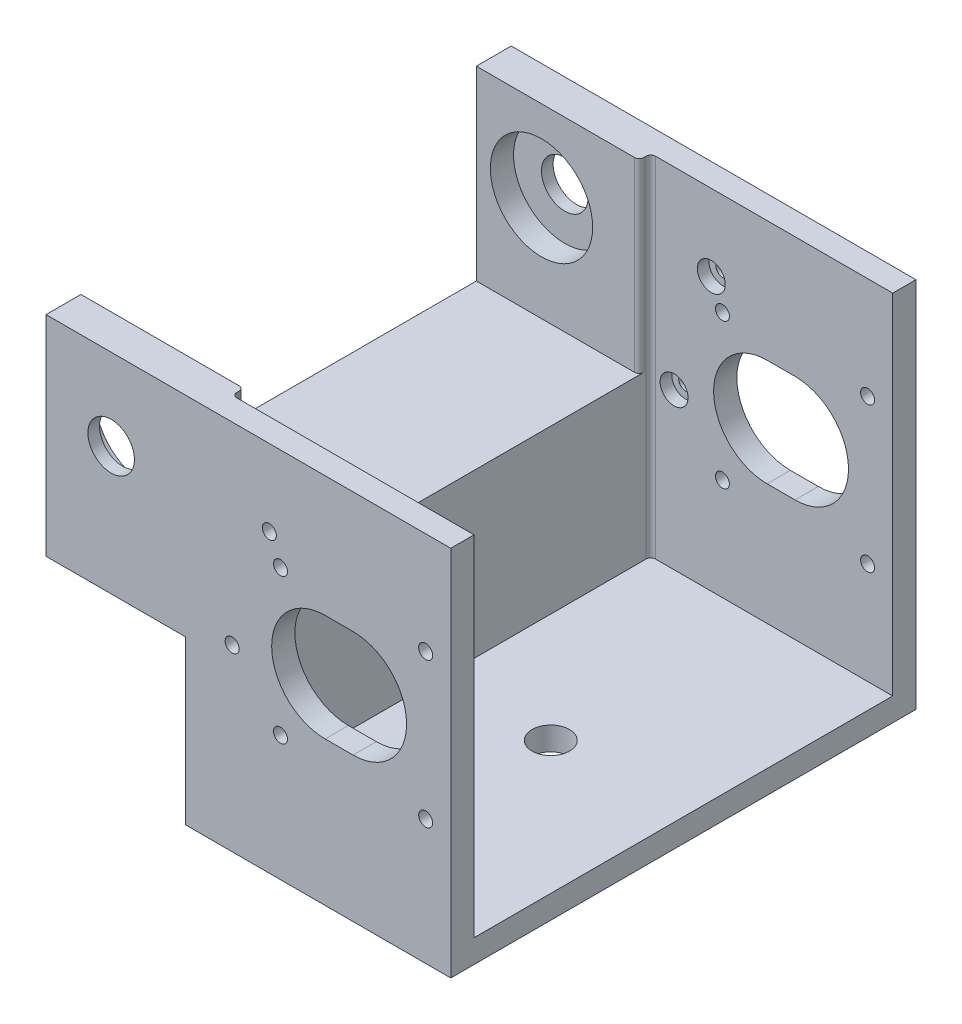
SolidWorks part; units mm, degrees
ref_plane "Front Plane" through (0, 0, 0) normal (0, 0, 1) x (1, 0, 0)
ref_plane "Top Plane" through (0, 0, 0) normal (0, 1, 0) x (1, 0, 0)
ref_plane "Right Plane" through (0, 0, 0) normal (1, 0, 0) x (0, 0, -1)
sketch "Sketch1" plane through (0, 0, 0) normal (0, 1, 0) x (1, 0, 0)
  line L1 (-28.5, 50) -> (28.5, 50)
  line L2 (-28.5, 50) -> (-28.5, -50)
  line L3 (-28.5, -50) -> (28.5, -50)
  line L4 (28.5, 50) -> (28.5, -50)
  line L5 (-28.5, 50) -> (28.5, -50) construction
  line L6 (-28.5, -50) -> (28.5, 50) construction
  point P0 (0, 0)
  dimension "D1" = 100
  dimension "D2" = 57
extrude "Boss-Extrude1" add sketch "Sketch1" along normal blind 80
sketch "Sketch3" plane through (28.5, 40, 0) normal (-1, 0, 0) x (0, 1, 0)
  line L1 (40, 45) -> (-35, 45)
  line L2 (40, 45) -> (40, -45)
  line L3 (40, -45) -> (-35, -45)
  line L4 (-35, 45) -> (-35, -45)
  line L5 (40, 45) -> (-35, -45) construction
  line L6 (40, -45) -> (-35, 45) construction
  line L10 (40, -50) -> (40, 50) construction
  line L11 (-40, -50) -> (-40, 50) construction
  line L12 (40, 50) -> (-40, 50) construction
  line L13 (40, -50) -> (-40, -50) construction
  point P0 (2.5, 0)
  dimension "D1" = 5
  dimension "D2" = 5
  dimension "D3" = 5
extrude "Cut-Extrude1" cut sketch "Sketch3" along normal blind 52
sketch "Sketch4" plane through (-40, 5, 0) normal (0, -1, 0) x (-1, 0, 0)
  line L0 (-40, 0) -> (-40, 10) construction
  circle A0 centre (-40, 0) radius 4.025
  circle A1 centre (-40, 10) radius 1.5 construction
  circle A2 centre (-30, 0) radius 1.5 construction
  circle A3 centre (-40, -10) radius 1.5 construction
  circle A4 centre (-50, 0) radius 1.5 construction
  dimension "D1" = 8.05
  dimension "D2" = 3
  dimension "D3" = 10
  dimension "D4" = 4
extrude "Cut-Extrude2" cut sketch "Sketch4" along normal through all
sketch "Sketch7" plane through (-28.5, 0, 0) normal (-1, 0, 0) x (0, 0, 1)
  line L0 (50, 80) -> (50, 0) construction
  line L1 (-50, 80) -> (-42.5, 80)
  line L2 (-50, 80) -> (-50, 35)
  line L4 (-42.5, 80) -> (-42.5, 40)
  line L5 (50, 80) -> (42.5, 80)
  line L6 (50, 80) -> (50, 35)
  line L8 (42.5, 80) -> (42.5, 40)
  line L9 (-50, 80) -> (50, 80) construction
  line L11 (-42.5, 40) -> (42.5, 40)
  line L13 (-50, 35) -> (50, 35)
  dimension "D1" = 7.5
  dimension "D2" = 40
  dimension "D3" = 5
extrude "Boss-Extrude2" add sketch "Sketch7" along normal blind 30
sketch "Sketch8" plane through (-28.5, 0, 0) normal (-1, 0, 0) x (0, 0, 1)
  line L4 (-42.5, 80) -> (-42.5, 40)
  line L5 (-42.5, 40) -> (42.5, 40)
  line L6 (42.5, 40) -> (42.5, 80)
  line L7 (42.5, 80) -> (-42.5, 80)
  line L8 (-42.5, 80) -> (-42.5, 40)
  line L9 (-42.5, 40) -> (42.5, 40)
  line L10 (42.5, 40) -> (42.5, 80)
  line L11 (42.5, 80) -> (-42.5, 80)
  dimension "D1" = 0
extrude "Cut-Extrude5" cut sketch "Sketch8" against normal up to next
sketch "Sketch5" plane through (0, 0, -50) normal (0, 0, -1) x (-1, 0, 0)
  line L0 (-4.5, 42.5) -> (30.0759, 42.5) construction
  line L1 (-4.5, 42.5) -> (-4.5, 17.143) construction
  line L2 (-28.5, 80) -> (58.5, 80) construction
  line L3 (-28.5, 80) -> (58.5, 80) construction
  line L4 (58.5, 80) -> (58.5, 35) construction
  line L5 (-23.1, 58.1) -> (-17.1, 58.1) construction
  line L6 (-23.1, 59.6) -> (-17.1, 59.6) construction
  line L7 (-23.1, 56.6) -> (-17.1, 56.6) construction
  line L8 (-28.5, 80) -> (-28.5, 0) construction
  line L9 (-1.5, 42.5) -> (-7.5, 42.5) construction
  line L10 (-1.5, 31) -> (-7.5, 31)
  line L11 (-1.5, 54) -> (-7.5, 54)
  line L12 (-23.1, 26.9) -> (-17.1, 26.9) construction
  line L13 (-23.1, 25.4) -> (-17.1, 25.4) construction
  line L14 (-23.1, 28.4) -> (-17.1, 28.4) construction
  line L15 (14.1, 26.9) -> (8.1, 26.9) construction
  line L16 (14.1, 25.4) -> (8.1, 25.4) construction
  line L17 (14.1, 28.4) -> (8.1, 28.4) construction
  line L18 (14.1, 58.1) -> (8.1, 58.1) construction
  line L19 (14.1, 59.6) -> (8.1, 59.6) construction
  line L20 (14.1, 56.6) -> (8.1, 56.6) construction
  line L21 (28.5, 35) -> (28.5, 0) construction
  circle A5 centre (44.5, 62.5) radius 5
  arc A7 (-23.1, 59.6) -> (-23.1, 56.6) centre (-23.1, 58.1) ccw construction
  arc A8 (-17.1, 56.6) -> (-17.1, 59.6) centre (-17.1, 58.1) ccw construction
  arc A9 (-1.5, 31) -> (-1.5, 54) centre (-1.5, 42.5) ccw
  arc A10 (-7.5, 54) -> (-7.5, 31) centre (-7.5, 42.5) ccw
  arc A11 (-23.1, 25.4) -> (-23.1, 28.4) centre (-23.1, 26.9) cw construction
  arc A12 (-17.1, 28.4) -> (-17.1, 25.4) centre (-17.1, 26.9) cw construction
  arc A13 (14.1, 25.4) -> (14.1, 28.4) centre (14.1, 26.9) ccw construction
  arc A14 (8.1, 28.4) -> (8.1, 25.4) centre (8.1, 26.9) ccw construction
  arc A15 (14.1, 59.6) -> (14.1, 56.6) centre (14.1, 58.1) cw construction
  arc A16 (8.1, 56.6) -> (8.1, 59.6) centre (8.1, 58.1) cw construction
  circle A17 centre (-23.1, 58.1) radius 1.5
  circle A18 centre (8.1, 58.1) radius 1.5
  circle A19 centre (8.1, 26.9) radius 1.5
  circle A20 centre (-23.1, 26.9) radius 1.5
  circle A21 centre (10.5, 63.6) radius 1.5
  circle A22 centre (18.5, 38.5) radius 1.5
  point P2 (-20.1, 58.1)
  point P8 (-20.1, 42.5)
  point P13 (-4.5, 42.5)
  point P31 (-20.1, 26.9)
  point P38 (11.1, 26.9)
  point P45 (11.1, 58.1)
  point P62 (20.1103, 62.5)
  point P63 (23.3045, 42.5)
  point P66 (0, 0)
  point P67 (0, 0)
  point P68 (0, 0)
  point P69 (14.5134, 61.1)
  dimension "D5" = 15.6
  dimension "D8" = 6
  dimension "D9" = 10
  dimension "D2" = 1.5
  dimension "D7" = 11.5
  dimension "D12" = 24
  dimension "D13" = 3
  dimension "D16" = 4
  dimension "D3" = 15.6
  dimension "D4" = 6
  dimension "D6" = 37.5
  dimension "D10" = 17.5
  dimension "D11" = 14
  dimension "D14" = 10
  dimension "D15" = 4
  dimension "D17" = 8
extrude "Cut-Extrude3" cut sketch "Sketch5" against normal through all
sketch "Sketch9" plane through (0, 0, 0) normal (0, 0, 1) x (1, 0, 0)
  circle A0 centre (-44.5, 62.5) radius 11
  circle A1 centre (-10.5, 63.6) radius 3
  circle A2 centre (-18.5, 38.5) radius 3
  dimension "D1" = 22
  dimension "D2" = 6
extrude "Cut-Extrude6" cut sketch "Sketch9" against normal mid plane 95
fillet "Fillet1" radius 1 4 edges at (-23.5, 42.5, 45) (-23.5, 60, 42.5) (-23.5, 42.5, -45) (-23.5, 60, -42.5)
